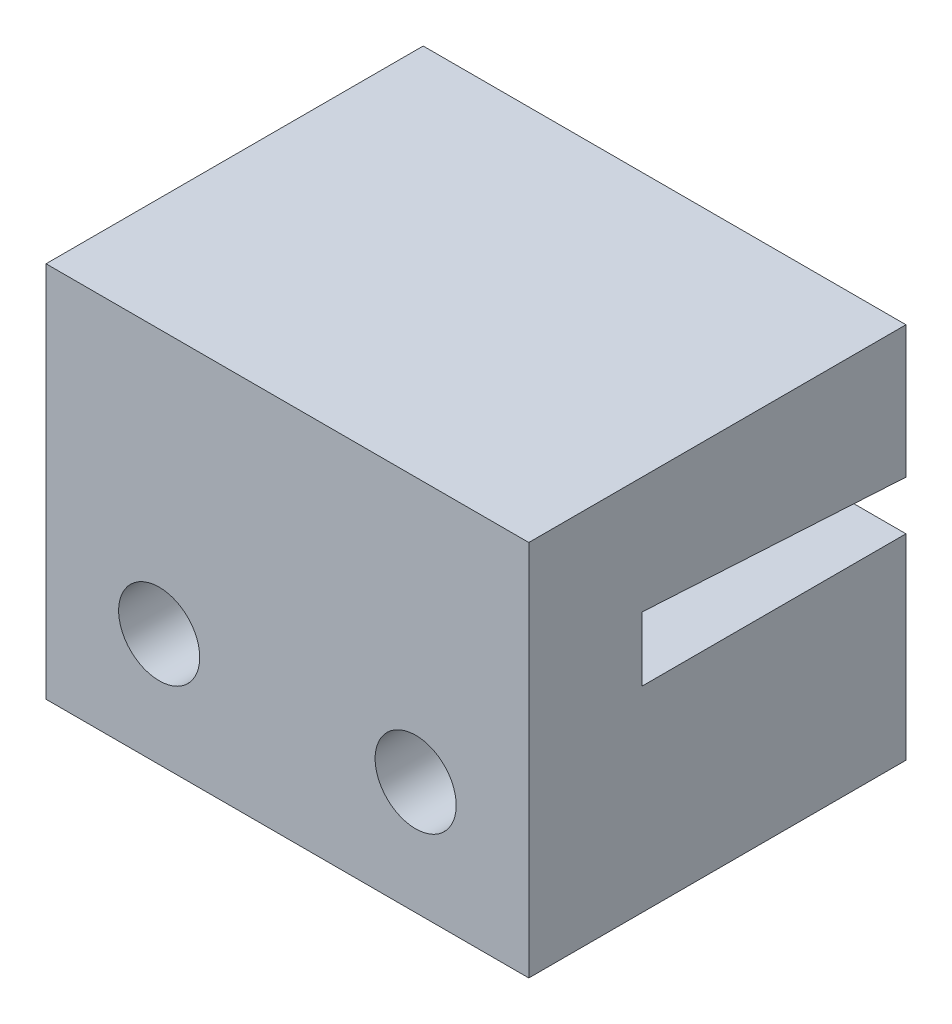
SolidWorks part; units mm, degrees
ref_plane "Front Plane" through (0, 0, 0) normal (0, 0, 1) x (1, 0, 0)
ref_plane "Top Plane" through (0, 0, 0) normal (0, 1, 0) x (1, 0, 0)
ref_plane "Right Plane" through (0, 0, 0) normal (1, 0, 0) x (0, 0, -1)
sketch "Sketch1" plane through (0, 0, 0) normal (0, 0, 1) x (1, 0, 0)
  line L0 (-6.4, 4) -> (-6.4, -1)
  line L1 (-6.4, -4) -> (6.4, -4)
  line L2 (-6.4, -4) -> (-6.4, 4)
  line L3 (-6.4, 4) -> (6.4, 4)
  line L4 (6.4, -4) -> (6.4, 4)
  line L5 (-6.4, -4) -> (6.4, 4) construction
  line L6 (-6.4, 4) -> (6.4, -4) construction
  line L7 (-6.4, 4) -> (6.4, 4)
  line L8 (-6.4, 4) -> (-6.4, 2.5)
  line L9 (-6.4, 2.5) -> (6.4, 2.5)
  line L10 (6.4, 4) -> (6.4, 2.5)
  line L11 (-6.4, -4) -> (6.4, -4)
  line L12 (-6.4, -4) -> (-6.4, 1.2)
  line L13 (-6.4, 1.2) -> (6.4, 1.2)
  line L14 (6.4, -4) -> (6.4, 1.2)
  line L15 (-6.4, -1) -> (-3.4, -1)
  line L16 (6.4, -1) -> (3.4, -1)
  circle A0 centre (3.4, -1) radius 1.075
  circle A1 centre (-3.4, -1) radius 1.075
  point P0 (0, 0)
  dimension "D8" = 2.15
  dimension "D9" = 2.15
  dimension "D1" = 8
  dimension "D2" = 12.8
  dimension "D3" = 1.5
  dimension "D4" = 1.3
  dimension "D5" = 5
  dimension "D6" = 3
  dimension "D7" = 3
extrude "Boss-Extrude1" add sketch "Sketch1" along normal blind 10 contours L0 L9 L4 L3 | L2 L13 L4 L9 | A1 L2 L1 L4 A0 L14 L13 L0 | A1 | A0 region at (0, 3.25, 0) region at (0, 1.85, 0) region at (-3.4, 0.0446, 0) region at (2.3554, -1, 0) region at (0, -1.449, 0)
extrude "Boss-Extrude2" add sketch "Sketch1<3>" along normal blind 7 contours L2 L13 L4 L9 region at (0, 1.85, 0)
sketch "Sketch1<3>" plane through (0, 0, 0) normal (0, 0, 1) x (1, 0, 0) same geometry as "Sketch1"
extrude "Cut-Extrude1" cut sketch "Sketch1<5>" along normal blind 7 contours L2 L13 L4 L9 region at (0, 1.85, 0)
sketch "Sketch1<5>" plane through (0, 0, 0) normal (0, 0, 1) x (1, 0, 0) same geometry as "Sketch1"
extrude "Cut-Extrude2" cut sketch "Sketch1<6>" along normal blind 10 contours A0 | A1 region at (-3.4, 0.0446, 0) region at (2.3554, -1, 0)
sketch "Sketch1<6>" plane through (0, 0, 0) normal (0, 0, 1) x (1, 0, 0) same geometry as "Sketch1"
sketch "Sketch4" plane through (0, 4, 0) normal (0, 1, 0) x (1, 0, 0)
  line L0 (6.4, -10) -> (6.4, 0) construction
  line L1 (6.4, -10) -> (-6.4, -10)
  line L2 (6.4, -10) -> (6.4, 0)
  line L3 (6.4, 0) -> (-6.4, 0)
  line L4 (-6.4, -10) -> (-6.4, 0)
  line L5 (-6.4, -10) -> (6.4, -10) construction
  line L6 (-6.4, 0) -> (6.4, 0) construction
  line L7 (-6.4, -10) -> (-6.4, 0) construction
extrude "Boss-Extrude3" add sketch "Sketch4" along normal blind 1
sketch "Sketch6" plane through (6.4, 0, 0) normal (1, 0, 0) x (0, 0, -1)
  line L0 (0, 2.5) -> (-7, 2.9028)
  line L1 (-7, 2.9028) -> (-7, 2.5)
  line L2 (-7, 2.5) -> (0, 2.5)
  dimension "D1" = 0.4028
extrude "Cut-Extrude3" cut sketch "Sketch6" against normal blind 15
sketch "Sketch8" plane through (0, 5, 0) normal (0, 1, 0) x (1, 0, 0)
  line L1 (-6.4, 0) -> (6.4, 0)
  line L2 (-6.4, 0) -> (-6.4, -10)
  line L3 (-6.4, -10) -> (6.4, -10)
  line L4 (6.4, 0) -> (6.4, -10)
extrude "Boss-Extrude4" add sketch "Sketch8" along normal blind 1
